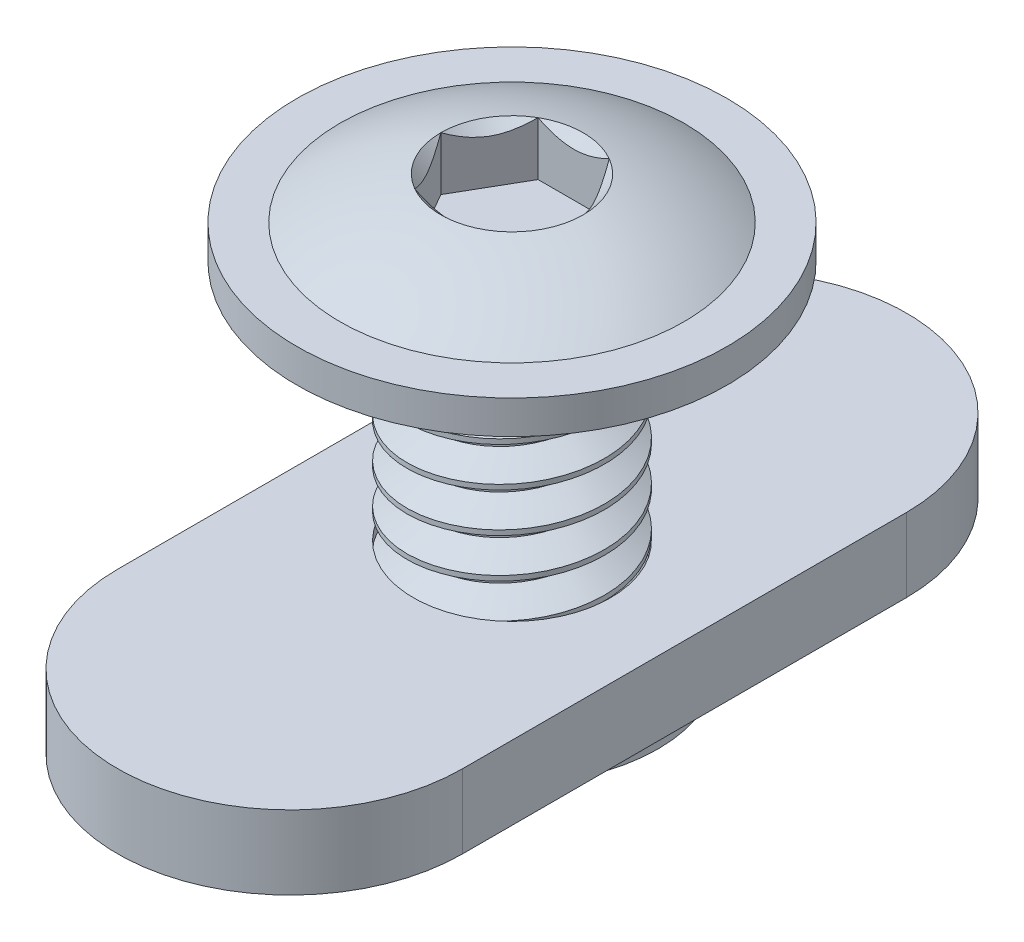
SolidWorks part; units mm, degrees
ref_plane "Front Plane" through (0, 0, 0) normal (0, 0, 1) x (1, 0, 0)
ref_plane "Top Plane" through (0, 0, 0) normal (0, 1, 0) x (1, 0, 0)
ref_plane "Right Plane" through (0, 0, 0) normal (1, 0, 0) x (0, 0, -1)
sketch "Sketch1" plane through (0, 0, 0) normal (0, 0, 1) x (1, 0, 0)
  line L0 (0, 0) -> (0, 53.1234) construction
  line L1 (0, 0) -> (-3.175, 0)
  line L2 (-3.175, 0) -> (-3.175, 12.7)
  line L3 (-3.175, 12.7) -> (-6.9215, 12.7)
  line L4 (-6.9215, 12.7) -> (-6.9215, 13.777)
  line L5 (-6.9215, 13.777) -> (-5.5372, 13.777)
  line L6 (0, 0) -> (0, 15.3924)
  arc A0 (-5.5372, 13.777) -> (0, 15.3924) centre (0, 5.0948) cw
  dimension "screw od" = 6.35
  dimension "head od" = 13.843
  dimension "D3" = 11.0744
  dimension "D4" = 1.077
  dimension "head height" = 2.6924
  dimension "screw length" = 12.7
sketch "Sketch2" plane through (0, 0, 0) normal (0, 0, 1) x (1, 0, 0)
  line L0 (0, 0) -> (0, 15.3924) construction
  line L1 (-3.175, 12.7) -> (-6.9215, 12.7) construction
  line L2 (0, 0) -> (-3.175, 0) construction
  line L3 (-3.175, 0) -> (-3.175, 12.7) construction
  line L4 (0, 0) -> (0, 12.7)
  line L5 (0, 12.7) -> (-3.175, 12.7)
  line L6 (0, 0) -> (-3.175, 0)
  line L7 (-3.175, 0) -> (-3.175, 12.7)
revolve "Revolve2" add sketch "Sketch2" angle 360 about L0
sketch "Sketch3" plane through (0, 12.7, 0) normal (0, 1, 0) x (1, 0, 0)
  circle A1 centre (0, 0) radius 3.175
  circle A2 centre (0, 0) radius 3.175
  dimension "D1" = 0
curve "Helix/Spiral1" pitch 1.27 height 17.4625 turns 13.75 parameters "pitch"=1.27
chamfer "Chamfer1" distance 1.27 angle 45 1 edges at (0, 0, -3.175)
sketch "Sketch4" plane through (0, 0, 0) normal (0, 0, 1) x (1, 0, 0)
  line L0 (3.175, 13.8112) -> (3.175, 12.7)
  line L1 (3.175, 12.7) -> (2.3501, 13.1762)
  line L2 (2.3501, 13.1762) -> (2.3501, 13.335)
  line L3 (2.3501, 13.335) -> (3.175, 13.8112)
  line L4 (2.3501, 13.2556) -> (3.175, 13.2556) construction
  line L5 (2.7626, 12.9381) -> (2.7626, 13.5731) construction
  line L7 (3.175, 12.7) -> (-3.175, 12.7) construction
  dimension "D1" = 60
  dimension "D2" = 0.1588
  dimension "D3" = 0.635
sweep "Cut-Sweep1" cut profiles "Sketch4" path "Helix/Spiral1"
sketch "Sketch5" plane through (0, 0, 0) normal (0, 0, 1) x (1, 0, 0)
  line L0 (0, 0) -> (0, 15.3924) construction
  line L1 (-3.175, 12.7) -> (-6.9215, 12.7) construction
  line L2 (-6.9215, 13.777) -> (-5.5372, 13.777) construction
  line L3 (-6.9215, 12.7) -> (-6.9215, 13.777) construction
  line L4 (0, 12.7) -> (0, 15.3924)
  line L5 (0, 12.7) -> (-6.9215, 12.7)
  line L6 (-6.9215, 13.777) -> (-5.5372, 13.777)
  line L7 (-6.9215, 12.7) -> (-6.9215, 13.777)
  arc A0 (0, 15.3924) -> (-5.5372, 13.777) centre (0, 5.0948) ccw construction
  arc A1 (0, 15.3924) -> (-5.5372, 13.777) centre (0, 5.0948) ccw
revolve "Revolve3" add sketch "Sketch5" angle 360 about L0
ref_plane "Plane1" through (0, 15.3924, 0) normal (0, 1, 0) x (-1, 0, 0)
sketch "Sketch6" plane through (0, 15.3924, 0) normal (0, 1, 0) x (-1, 0, 0)
  line L1 (1.1457, 1.9844) -> (-1.1457, 1.9844)
  line L2 (-1.1457, 1.9844) -> (-2.2914, 0)
  line L3 (-2.2914, 0) -> (-1.1457, -1.9844)
  line L4 (-1.1457, -1.9844) -> (1.1457, -1.9844)
  line L5 (1.1457, -1.9844) -> (2.2914, 0)
  line L6 (2.2914, 0) -> (1.1457, 1.9844)
  circle A0 centre (0, 0) radius 1.9844 construction
  dimension "hex" = 3.9688
extrude "Cut-Extrude1" cut sketch "Sketch6" against normal blind 1.9844
ref_plane "Plane2" through (0, 15.1342, 0) normal (0, 1, 0) x (-1, 0, 0)
sketch "Sketch7" plane through (0, 15.1342, 0) normal (0, 1, 0) x (-1, 0, 0)
  circle A0 centre (0, 0) radius 2.2914
extrude "Cut-Extrude2" cut sketch "Sketch7" against normal up to surface (1.7262 mm away) draft 45 and the other way through all
ref_plane "Plane3" through (0, 3.175, 0) normal (0, -1, 0) x (1, 0, 0)
sketch "Sketch8" plane through (0, 3.175, 0) normal (0, -1, 0) x (1, 0, 0)
  line L0 (0, -7.1437) -> (0, 7.1437) construction
  line L2 (-5.5563, 7.1437) -> (-5.5563, -7.1437)
  line L4 (5.5563, 7.1437) -> (5.5563, -7.1437)
  circle A0 centre (0, 0) radius 3.175
  arc A1 (-5.5563, 7.1437) -> (5.5563, 7.1437) centre (0, 7.1437) cw
  arc A2 (-5.5563, -7.1437) -> (5.5563, -7.1437) centre (0, -7.1437) ccw
  dimension "D1" = 6.35
  dimension "D3" = 25.4
  dimension "D2" = 11.1125
extrude "Extrude1" add sketch "Sketch8" along normal mid plane 3.4544 separate body
sketch "Sketch9" plane through (0, 1.4478, 0) normal (0, -1, 0) x (1, 0, 0)
  line L2 (5.5563, -7.1437) -> (5.5563, 7.1437)
  line L3 (-5.5563, 7.1437) -> (-5.5563, -7.1437)
  line L4 (5.5563, -7.1437) -> (5.5563, 7.1437)
  line L5 (-5.5563, 7.1437) -> (-5.5563, -7.1437)
  arc A2 (-5.5563, -7.1437) -> (5.5563, -7.1437) centre (0, -7.1437) ccw
  arc A3 (5.5563, 7.1437) -> (-5.5563, 7.1437) centre (0, 7.1437) ccw
  arc A4 (-5.5563, -7.1437) -> (5.5563, -7.1437) centre (0, -7.1437) ccw
  arc A5 (5.5563, 7.1437) -> (-5.5563, 7.1437) centre (0, 7.1437) ccw
  circle A6 centre (0, 0) radius 4.699
  circle A7 centre (0, 0) radius 4.699
  dimension "D1" = 0
  dimension "D2" = 1.524
extrude "Cut-Extrude3" cut sketch "Sketch9" against normal offset from surface (1.0795 mm away) 2.3749 up to face at (0, 4.9022, 0)
sketch "Sketch10" [suppressed] plane through (0, 7.9375, 0) normal (0, -1, 0) x (1, 0, 0)
  line L0 (-8.255, -12.3888) -> (-8.255, 2.8511)
  line L1 (8.255, 2.8511) -> (8.255, -12.3888)
  line L2 (-14.9844, 7.9311) -> (0, 7.9311) construction
  circle A0 centre (0, 0) radius 3.9688
  arc A1 (8.255, 2.8511) -> (-8.255, 2.8511) centre (0, -1.316) ccw
  arc A2 (-8.255, -12.3888) -> (8.255, -12.3888) centre (0, -8.2217) ccw
  dimension "D2" = 3.9624
  dimension "D3" = 16.51
  dimension "D4" = 5.08
  dimension "D5" = 6.35
  dimension "D1" = 25.4
extrude "Extrude2" [suppressed] add sketch "Sketch10" along normal mid plane 5.3594 separate body
sketch "Sketch11" [suppressed] plane through (0, 5.2578, 0) normal (0, -1, 0) x (1, 0, 0)
  line L2 (8.255, -12.3888) -> (8.255, 2.8511)
  line L3 (-8.255, 2.8512) -> (-8.255, -12.3888)
  line L4 (8.255, -12.3888) -> (8.255, 2.8511)
  line L5 (-8.255, 2.8512) -> (-8.255, -12.3888)
  circle A2 centre (0, 0) radius 5.4927
  circle A3 centre (0, 0) radius 5.4927
  arc A5 (-8.255, -12.3888) -> (8.255, -12.3888) centre (0, -8.2217) ccw
  arc A6 (8.255, 2.8511) -> (-8.255, 2.8512) centre (0, -1.316) ccw
  arc A7 (-8.255, -12.3888) -> (8.255, -12.3888) centre (0, -8.2217) ccw
  arc A8 (8.255, 2.8511) -> (-8.255, 2.8512) centre (0, -1.316) ccw
  dimension "D1" = 1.524
  dimension "D2" = 0
extrude "Cut-Extrude4" [suppressed] cut sketch "Sketch11" against normal offset from surface (1.651 mm away) 3.7084
sketch "Sketch12" [suppressed] plane through (0, 0, 0) normal (0, 0, 1) x (1, 0, 0)
  line L0 (-6.7564, 17.78) -> (-5.4051, 17.78) construction
  line L1 (-6.7564, 17.78) -> (-5.4051, 17.78)
  line L2 (10.3378, 20.0315) -> (-10.3378, 20.0315) construction
  line L3 (0, 0) -> (0, 53.1234) construction
  line L4 (-3.9688, 15.875) -> (-6.7564, 15.875) construction
  line L5 (-9.398, 15.875) -> (-3.9688, 15.875)
  line L6 (-9.398, 15.875) -> (-9.398, 14.605)
  line L7 (-9.398, 14.605) -> (-3.9688, 14.605)
  line L8 (-3.9688, 15.875) -> (-3.9688, 14.605)
  arc A0 (0, 20.6375) -> (-5.4051, 17.78) centre (0, 14.0967) ccw construction
  arc A1 (-2.7496, 20.0315) -> (-5.4051, 17.78) centre (0, 14.0967) ccw
  arc A2 (-6.7564, 17.78) -> (-2.7496, 20.0315) centre (0, 10.4472) cw
  dimension "D1" = 9.398
  dimension "D2" = 1.27
revolve "Revolve4" [suppressed] add sketch "Sketch12" angle 360 about L0
sketch "Sketch13" [suppressed] plane through (0, 6.35, 0) normal (0, -1, 0) x (1, 0, 0)
  line L0 (-7.9375, 4.7562) -> (-7.9375, -17.4688)
  line L1 (7.9375, 4.7562) -> (7.9375, -17.4688)
  circle A0 centre (0, 0) radius 3.9688
  arc A1 (-7.9375, 4.7562) -> (7.9375, 4.7562) centre (0, -3.5782) cw
  arc A2 (-7.9375, -17.4688) -> (7.9375, -17.4688) centre (0, -9.1345) ccw
  dimension "D2" = 28.575
  dimension "D3" = 3.9624
  dimension "D4" = 7.9375
  dimension "D1" = 15.875
  dimension "D5" = 3.175
extrude "Extrude4" [suppressed] add sketch "Sketch13" along normal mid plane 5.8928 separate body
sketch "Sketch14" [suppressed] plane through (0, 3.4036, 0) normal (0, -1, 0) x (1, 0, 0)
  line L2 (-7.9375, 4.7561) -> (-7.9375, -17.4688)
  line L3 (7.9375, -17.4688) -> (7.9375, 4.7562)
  line L4 (-7.9375, 4.7561) -> (-7.9375, -17.4688)
  line L5 (7.9375, -17.4688) -> (7.9375, 4.7562)
  arc A2 (7.9375, 4.7562) -> (-7.9375, 4.7561) centre (0, -3.5782) ccw
  arc A3 (-7.9375, -17.4688) -> (7.9375, -17.4688) centre (0, -9.1345) ccw
  arc A4 (7.9375, 4.7562) -> (-7.9375, 4.7561) centre (0, -3.5782) ccw
  arc A5 (-7.9375, -17.4688) -> (7.9375, -17.4688) centre (0, -9.1345) ccw
  circle A6 centre (0, 0) radius 5.4927
  circle A7 centre (0, 0) radius 5.4927
  dimension "D1" = 0
  dimension "D2" = 1.524
extrude "Cut-Extrude7" [suppressed] cut sketch "Sketch14" against normal offset from surface (1.8034 mm away) 4.0894
sketch "Sketch15" [suppressed] plane through (0, 0, 0) normal (0, 0, 1) x (1, 0, 0)
  line L0 (-6.6675, 19.6774) -> (-5.334, 19.6774) construction
  line L1 (-6.6675, 19.6774) -> (-5.334, 19.6774)
  line L2 (9.2481, 22.5402) -> (-9.2481, 22.5402) construction
  line L3 (0, 0) -> (0, 53.1234) construction
  arc A0 (0, 22.9997) -> (-5.334, 19.6774) centre (0, 17.0567) ccw construction
  arc A1 (-2.2914, 22.5402) -> (-5.334, 19.6774) centre (0, 17.0567) ccw
  arc A2 (-2.2914, 22.5402) -> (-6.6675, 19.6774) centre (0, 14.2615) ccw
revolve "Revolve5" [suppressed] add sketch "Sketch15" angle 360 about L0
sketch "Sketch16" [suppressed] plane through (0, 3.175, 0) normal (0, -1, 0) x (1, 0, 0)
  line L0 (-6.3881, 8.443) -> (-6.3881, -33.843)
  line L1 (6.3881, 8.443) -> (6.3881, -33.843)
  line L2 (0, -25.4) -> (0, 0) construction
  line L3 (0, -12.7) -> (-6.3881, -12.7) construction
  line L4 (-6.3881, -27.1355) -> (-6.3881, 1.7355) construction
  circle A0 centre (0, 0) radius 3.175
  circle A1 centre (0, -25.4) radius 3.175
  arc A2 (-6.3881, 8.443) -> (6.3881, 8.443) centre (0, 1.7355) cw
  arc A3 (-6.3881, -33.843) -> (6.3881, -33.843) centre (0, -27.1355) ccw
  dimension "D1" = 25.4
  dimension "D2" = 6.35
  dimension "D4" = 47.3964
  dimension "D3" = 12.7762
  dimension "D5" = 2.5552
extrude "Extrude5" [suppressed] add sketch "Sketch16" along normal mid plane 4.0894 separate body
sketch "Sketch17" [suppressed] plane through (0, 1.1303, 0) normal (0, -1, 0) x (1, 0, 0)
  line L2 (-6.3881, 8.443) -> (-6.3881, -33.843)
  line L3 (6.3881, -33.843) -> (6.3881, 8.443)
  line L4 (-6.3881, 8.443) -> (-6.3881, -33.843)
  line L5 (6.3881, -33.843) -> (6.3881, 8.443)
  arc A2 (6.3881, 8.443) -> (-6.3881, 8.443) centre (0, 1.7355) ccw
  arc A3 (-6.3881, -33.843) -> (6.3881, -33.843) centre (0, -27.1355) ccw
  arc A4 (6.3881, 8.443) -> (-6.3881, 8.443) centre (0, 1.7355) ccw
  arc A5 (-6.3881, -33.843) -> (6.3881, -33.843) centre (0, -27.1355) ccw
  circle A6 centre (0, -25.4) radius 4.699
  circle A7 centre (0, -25.4) radius 4.699
  circle A10 centre (0, 0) radius 4.699
  circle A11 centre (0, 0) radius 4.699
  dimension "D1" = 0
  dimension "D2" = 1.524
  dimension "D3" = 1.524
pattern_linear "LPattern1" [suppressed] count 2 spacing 25.4
extrude "Cut-Extrude9" [suppressed] cut sketch "Sketch17" against normal offset from surface (1.4224 mm away) 2.667
sketch "Sketch18" [suppressed] plane through (0, 7.9375, 0) normal (0, -1, 0) x (1, 0, 0)
  line L0 (-7.9375, 13.462) -> (-7.9375, -51.562)
  line L1 (7.9375, 13.462) -> (7.9375, -51.562)
  line L2 (0, 0) -> (0, -38.1) construction
  line L3 (0, -19.05) -> (-7.9375, -19.05) construction
  line L4 (0, -19.05) -> (7.9375, -19.05) construction
  circle A0 centre (0, 0) radius 3.9688
  circle A1 centre (0, -38.1) radius 3.9688
  arc A2 (-7.9375, 13.462) -> (7.9375, 13.462) centre (0, 5.1276) cw
  arc A3 (-7.9375, -51.562) -> (7.9375, -51.562) centre (0, -43.2276) ccw
  dimension "D1" = 38.1
  dimension "D2" = 7.9375
  dimension "D4" = 3.175
  dimension "D5" = 71.374
  dimension "D3" = 15.875
extrude "Extrude6" [suppressed] add sketch "Sketch18" along normal mid plane 5.9944 separate body
sketch "Sketch19" [suppressed] plane through (0, 4.9403, 0) normal (0, -1, 0) x (1, 0, 0)
  line L2 (-7.9375, 13.462) -> (-7.9375, -51.562)
  line L3 (7.9375, -51.562) -> (7.9375, 13.462)
  line L4 (-7.9375, 13.462) -> (-7.9375, -51.562)
  line L5 (7.9375, -51.562) -> (7.9375, 13.462)
  arc A2 (7.9375, 13.462) -> (-7.9375, 13.462) centre (0, 5.1276) ccw
  arc A3 (-7.9375, -51.562) -> (7.9375, -51.562) centre (0, -43.2276) ccw
  arc A4 (7.9375, 13.462) -> (-7.9375, 13.462) centre (0, 5.1276) ccw
  arc A5 (-7.9375, -51.562) -> (7.9375, -51.562) centre (0, -43.2276) ccw
  circle A6 centre (0, 0) radius 5.4927
  circle A7 centre (0, 0) radius 5.4927
  circle A9 centre (0, -38.1) radius 5.4928
  circle A10 centre (0, -38.1) radius 5.4928
  dimension "D1" = 0
  dimension "D2" = 1.524
  dimension "D3" = 1.524
extrude "Cut-Extrude10" [suppressed] cut sketch "Sketch19" against normal offset from surface (2.1844 mm away) 3.81
pattern_linear "LPattern2" [suppressed] count 2 spacing 38.1
equation "\"D2@Sketch4\" = \"pitch@Helix/Spiral1\"*.125"
equation "\"D3@Sketch4\" = \"pitch@Helix/Spiral1\"*.5"
equation "\"D3@Helix/Spiral1\" = \"screw length@Sketch1\"+.18750"
equation "\"D1@Chamfer1\" = \"pitch@Helix/Spiral1\""
equation "\"D1@Cut-Extrude1\" = \"hex@Sketch6\"/2"
equation "\"D1@Sketch8\" = \"screw od@Sketch1\""
equation "\"D4@Sketch1\" = \"head height@Sketch1\"/2.5"
equation "\"D3@Sketch1\" = \"head od@Sketch1\"*.8"
equation "\"D5@Sketch10\" = \"screw od@Sketch1\""
equation "\"D4@Sketch10\" = \"D1@Sketch10\"*.2"
equation "\"D5@Sketch13\" = \"D1@Sketch13\"*.2"
equation "\"D5@Sketch16\" = \"D3@Sketch16\"*.2"
equation "\"D4@Sketch18\" = \"D3@Sketch18\"*.2"
